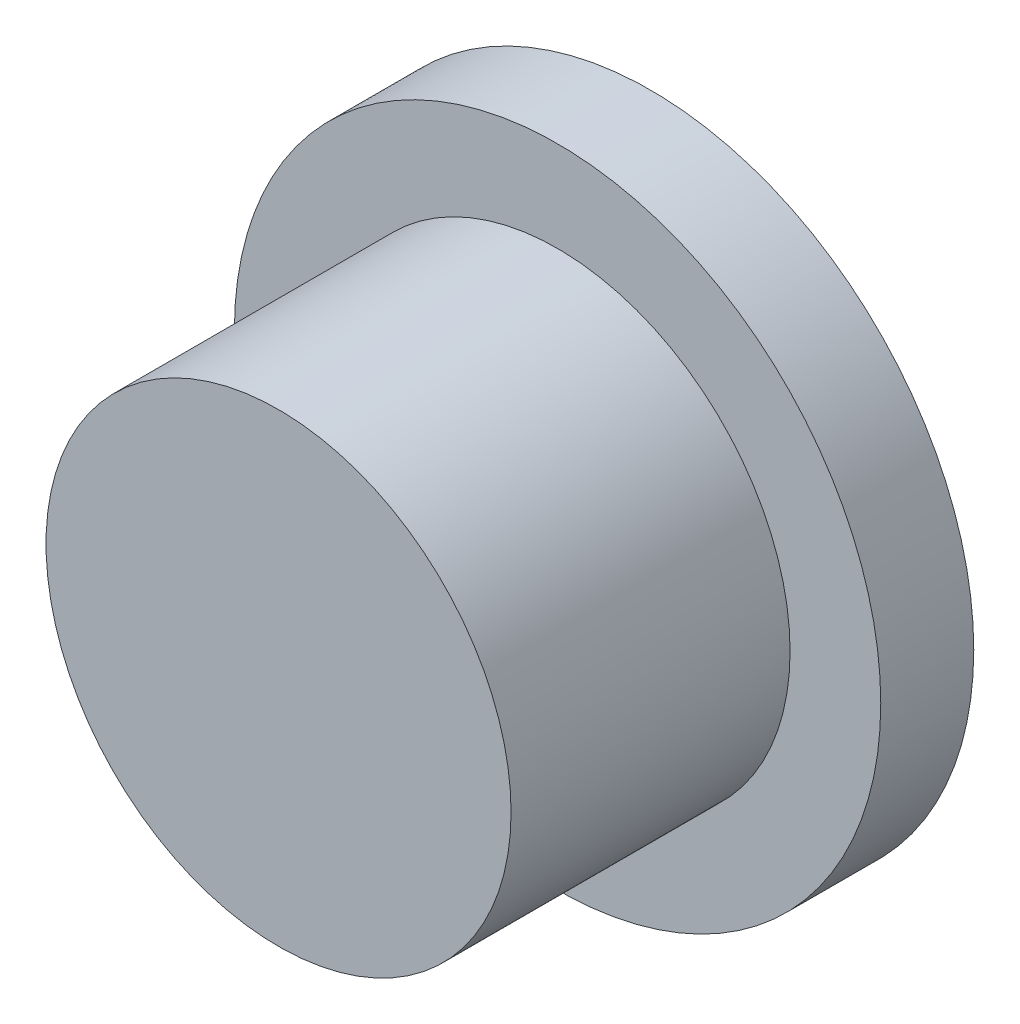
SolidWorks part; units mm, degrees
ref_plane "Ön Düzlem" through (0, 0, 0) normal (0, 0, 1) x (1, 0, 0)
ref_plane "Üst Düzlem" through (0, 0, 0) normal (0, 1, 0) x (1, 0, 0)
ref_plane "Sağ Düzlem" through (0, 0, 0) normal (1, 0, 0) x (0, 0, -1)
sketch "Çizim1" plane through (0, 0, 0) normal (0, 0, 1) x (1, 0, 0)
  circle A0 centre (0, 0) radius 6.95
  dimension "D1" = 13.9
extrude "Yükseklik-Ekstrüzyon1" add sketch "Çizim1" along normal blind 2
sketch "Çizim2" plane through (0, 0, 2) normal (0, 0, 1) x (1, 0, 0)
  circle A0 centre (0, 0) radius 5
  circle A1 centre (0, 0) radius 6.95
  circle A2 centre (0, 0) radius 6.95
  circle A3 centre (0, 0) radius 5
  dimension "D2" = 10
  dimension "D1" = 0
extrude "Yükseklik-Ekstrüzyon2" add sketch "Çizim2" along normal blind 6 contours A0 region at (0, 0, 2)
